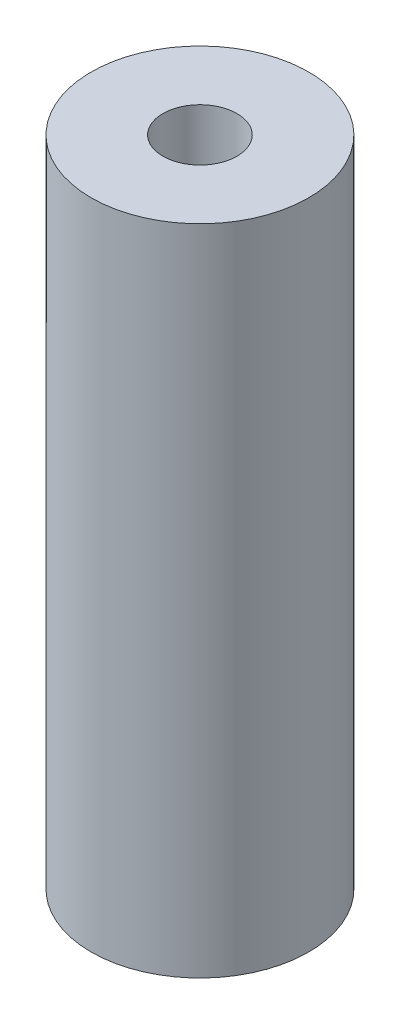
SolidWorks part; units mm, degrees
ref_plane "前视基准面" through (0, 0, 0) normal (0, 0, 1) x (1, 0, 0)
ref_plane "上视基准面" through (0, 0, 0) normal (0, 1, 0) x (1, 0, 0)
ref_plane "右视基准面" through (0, 0, 0) normal (1, 0, 0) x (0, 0, -1)
other "Configuration Table"
sketch "草图1" plane through (0, 0, 0) normal (0, 1, 0) x (1, 0, 0)
  circle A0 centre (0, 0) radius 1.25
  dimension "D1" = 2.5
extrude "凸台-拉伸1" add sketch "草图1" along normal blind 2
sketch "草图2" plane through (0, 2, 0) normal (0, 1, 0) x (1, 0, 0)
  circle A0 centre (0, 0) radius 2.5
  dimension "D1" = 5
extrude "凸台-拉伸2" add sketch "草图2" along normal blind 15
sketch "草图3" plane through (0, 17, 0) normal (0, 1, 0) x (1, 0, 0)
  circle A0 centre (0, 0) radius 0.85
  dimension "D1" = 1.7
extrude "切除-拉伸1" cut sketch "草图3" against normal blind 8
extrude "切除-拉伸2" cut sketch "草图1<3>" along normal blind 10
sketch "草图1<3>" plane through (0, 0, 0) normal (0, 1, 0) x (1, 0, 0) same geometry as "草图1"
